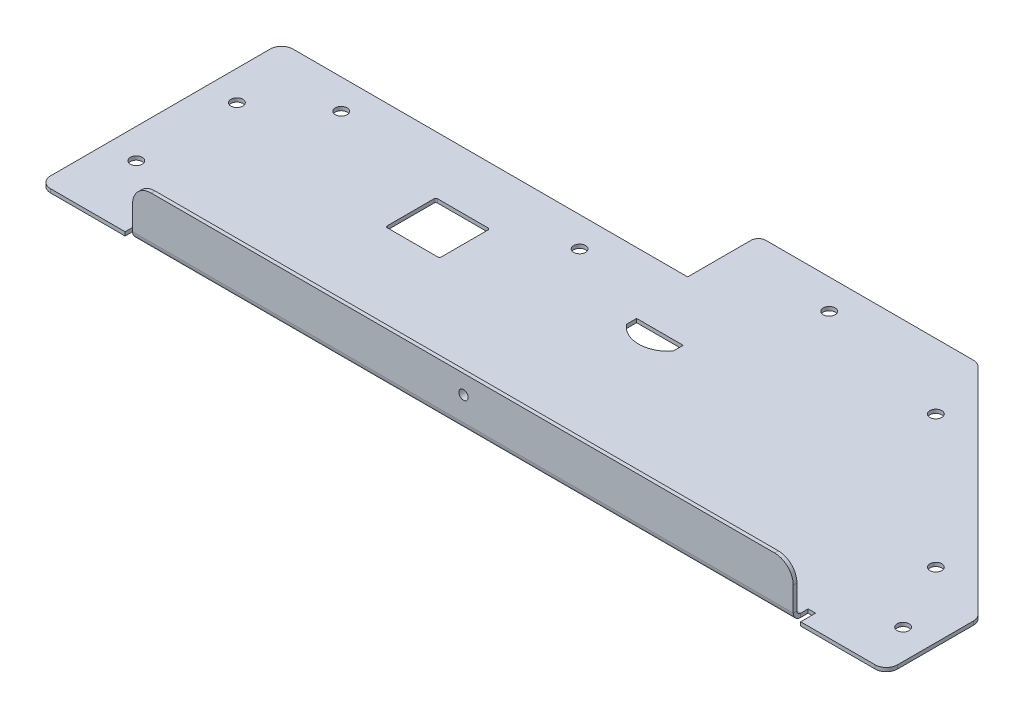
SolidWorks part; units mm, degrees
note: The reader was unsure of these and kept them because the rebuilt part matched: flange length of "边线-法兰1".
material "普通碳钢"
ref_plane "前视基准面" through (0, 0, 0) normal (0, 0, 1) x (1, 0, 0)
ref_plane "上视基准面" through (0, 0, 0) normal (0, 1, 0) x (1, 0, 0)
ref_plane "右视基准面" through (0, 0, 0) normal (1, 0, 0) x (0, 0, -1)
sketch "草图1" plane through (0, 0, 0) normal (0, 1, 0) x (1, 0, 0)
  line L0 (-322.3775, 0) -> (382.0821, 0) construction
  line L1 (0, 265.763) -> (0, -329.6125) construction
  line L2 (-113.67, 32.76) -> (-113.67, -26.24)
  line L3 (-110.67, -29.24) -> (110.67, -29.24)
  line L4 (113.67, -26.24) -> (113.67, -5.8826)
  line L5 (112.7913, -3.7613) -> (55.1487, 53.8813)
  line L6 (53.0274, 54.76) -> (-2.67, 54.76)
  line L7 (-4.67, 52.76) -> (-4.67, 35.76)
  line L8 (-4.67, 35.76) -> (-110.67, 35.76)
  line L9 (10.63, 19.26) -> (-1.87, 19.26)
  line L10 (-1.87, 19.26) -> (-1.87, 16.56)
  line L12 (10.63, 16.56) -> (10.63, 19.26)
  line L13 (-42.37, 19.86) -> (-42.37, 7.36)
  line L14 (-42.87, 6.86) -> (-56.37, 6.86)
  line L15 (-56.87, 7.36) -> (-56.87, 19.86)
  line L16 (-56.37, 20.36) -> (-42.87, 20.36)
  arc A0 (10.63, 16.56) -> (-1.87, 16.56) centre (4.38, 21.5537) cw
  arc A1 (-110.67, -29.24) -> (-113.67, -26.24) centre (-110.67, -26.24) cw
  arc A2 (-113.67, 32.76) -> (-110.67, 35.76) centre (-110.67, 32.76) cw
  arc A4 (55.1487, 53.8813) -> (53.0274, 54.76) centre (53.0274, 51.76) ccw
  arc A5 (113.67, -5.8826) -> (112.7913, -3.7613) centre (110.67, -5.8826) ccw
  arc A6 (110.67, -29.24) -> (113.67, -26.24) centre (110.67, -26.24) ccw
  circle A7 centre (-105.67, -11.24) radius 1.6
  circle A8 centre (-105.67, 15.76) radius 1.6
  circle A9 centre (-89.67, 27.76) radius 1.6
  circle A10 centre (-25.67, 27.76) radius 1.6
  circle A11 centre (22.33, 46.76) radius 1.6
  circle A12 centre (60.5163, 37.2) radius 1.6
  circle A13 centre (96.1163, 1.6) radius 1.6
  circle A14 centre (105.67, -16.74) radius 1.6
  arc A15 (-56.37, 20.36) -> (-56.87, 19.86) centre (-56.37, 19.86) ccw
  arc A16 (-56.87, 7.36) -> (-56.37, 6.86) centre (-56.37, 7.36) ccw
  arc A17 (-42.87, 6.86) -> (-42.37, 7.36) centre (-42.87, 7.36) ccw
  arc A18 (-42.37, 19.86) -> (-42.87, 20.36) centre (-42.87, 19.86) ccw
  arc A19 (-2.67, 54.76) -> (-4.67, 52.76) centre (-2.67, 52.76) ccw
  point P22 (4.38, 19.26)
  point P30 (54.27, 54.76)
  dimension "D11" = 8
  dimension "D13" = 3
  dimension "D18" = 3.2
  dimension "D32" = 0.5
  dimension "D33" = 2
  dimension "D34" = 3
  dimension "D1" = 65
  dimension "D2" = 109
  dimension "D3" = 19
  dimension "D4" = 58.94
  dimension "D5" = 227.34
  dimension "D6" = 45
  dimension "D7" = 40.5
  dimension "D8" = 12.5
  dimension "D9" = 14.5
  dimension "D10" = 13.5
  dimension "D12" = 2.7
  dimension "D14" = 18
  dimension "D15" = 27
  dimension "D16" = 24
  dimension "D17" = 64
  dimension "D19" = 8
  dimension "D20" = 8
  dimension "D21" = 27
  dimension "D22" = 8
  dimension "D23" = 8
  dimension "D24" = 8
  dimension "D25" = 17.56
  dimension "D26" = 35.6
  dimension "D27" = 12.5
  dimension "D28" = 8
  dimension "D29" = 15.4
  dimension "D30" = 16.5
  dimension "D31" = 56.8
base flange "基体-法兰1" sketch "草图1" thickness 1 reverse thickness direction no parameters "D1"=1
edge flange "边线-法兰1" sketch "草图4" flange angle 90 flange length 13.5 flange position material inside bend radius 1 thickness 1 relief rectangular parameters "D6"=10
sketch "草图4" plane through (0, 0, 29.24) normal (0, 0, 1) x (1, 0, 0)
  line L2 (-88.67, 0) -> (-88.67, 7.5)
  line L3 (-83.67, 12.5) -> (83.67, 12.5)
  line L4 (88.67, 7.5) -> (88.67, 0)
  line L5 (-110.67, 0) -> (110.67, 0) construction
  line L6 (-88.67, 0) -> (88.67, 0)
  line L7 (113.67, -1) -> (113.67, 0) construction
  line L8 (-113.67, -1) -> (-113.67, 0) construction
  line L9 (-110.67, -1) -> (110.67, -1) construction
  arc A0 (83.67, 12.5) -> (88.67, 7.5) centre (83.67, 7.5) cw
  arc A1 (-83.67, 12.5) -> (-88.67, 7.5) centre (-83.67, 7.5) ccw
  dimension "D3" = 5
  dimension "D1" = 25
  dimension "D2" = 25
  dimension "D4" = 13.5
bend "边线折弯1" bend radius 1 bend angle 90 parameters "D5"=1
sketch "草图5" plane through (0, 0, 28.24) normal (0, 0, -1) x (-1, 0, 0)
  line L0 (-88.67, -1) -> (88.67, -1) construction
  line L1 (113.67, -1) -> (113.67, 0) construction
  circle A0 centre (-0.17, 7.5) radius 3
  dimension "D1" = 6
  dimension "D2" = 8.5
  dimension "D3" = 113.84
extrude "凸台-拉伸1" add sketch "草图5" along normal blind 2
hole_wizard "M3 螺纹孔1" positions "草图6" profile "草图7" tap size "M3" standard "GB" end condition through all
sketch "草图6" plane through (0, 0, 26.24) normal (0, 0, -1) x (-1, 0, 0)
  point P0 (-0.17, 7.5)
sketch "草图7" plane through (0.17, 7.5, 26.24) normal (1, 0, 0) x (0, 1, 0)
  line L0 (0, 0) -> (0, 3)
  line L1 (0, 3) -> (1.25, 3)
  line L2 (1.25, 3) -> (1.25, 0)
  line L5 (1.25, 0) -> (0, 0)
  line L11 (0, -6.35) -> (0, 107.95) construction
  dimension "通孔螺纹孔钻头直径" = 2.5
  dimension "通孔螺纹孔钻头深度" = 3
cosmetic thread "孔螺蚊线1"
sketch "折弯-线1" [suppressed] plane through (0, 0, 0) normal (0, 1, 0) x (1, 0, 0)
sketch "边界框1" [suppressed] plane through (0, 0, 0) normal (0, 1, 0) x (1, 0, 0)
sheet metal parameters "钣金6" thickness 1 parameters "D1"=1
flat pattern "平板型式6" [suppressed]
sketch "折弯-线2" plane through (0, 0, 0) normal (0, 1, 0) x (1, 0, 0)
sketch3d "边界框2" [suppressed]
  line L0 (113.67, -31.612, 0) -> (-113.67, -31.612, 0) construction
  line L1 (113.67, 52.388, 0) -> (-113.67, 52.388, 0) construction
  line L2 (113.67, -31.612, 0) -> (113.67, 52.388, 0) construction
  line L3 (-113.67, -31.612, 0) -> (-113.67, 52.388, 0) construction
sheet metal parameters "钣金7" thickness 1 parameters "D1"=1
flat pattern "平板型式6" [suppressed]
sketch "折弯-线2" plane through (0, 0, 0) normal (0, 1, 0) x (1, 0, 0)
sketch3d "边界框2" [suppressed]
  line L0 (113.67, -31.612, 0) -> (-113.67, -31.612, 0) construction
  line L1 (113.67, 52.388, 0) -> (-113.67, 52.388, 0) construction
  line L2 (113.67, -31.612, 0) -> (113.67, 52.388, 0) construction
  line L3 (-113.67, -31.612, 0) -> (-113.67, 52.388, 0) construction
bend of the flat pattern "展开-<边线折弯1>1"
sheet metal parameters "钣金8" thickness 1 parameters "D1"=1
flat pattern "平板型式6" [suppressed]
sketch "折弯-线2" plane through (0, 0, 0) normal (0, 1, 0) x (1, 0, 0)
sketch3d "边界框2" [suppressed]
  line L0 (113.67, -31.612, 0) -> (-113.67, -31.612, 0) construction
  line L1 (113.67, 52.388, 0) -> (-113.67, 52.388, 0) construction
  line L2 (113.67, -31.612, 0) -> (113.67, 52.388, 0) construction
  line L3 (-113.67, -31.612, 0) -> (-113.67, 52.388, 0) construction
bend of the flat pattern "展开-<边线折弯1>1"
sheet metal parameters "钣金9" thickness 1 parameters "D1"=1
flat pattern "平板型式6"
sketch "折弯-线2" plane through (0, 0, 0) normal (0, 1, 0) x (-1, 0, 0)
  line L0 (88.67, 28.4181) -> (-88.67, 28.4181) construction
  line L1 (88.67, 28.4181) -> (-88.67, 28.4181) construction
sketch3d "边界框2" [suppressed]
  line L0 (3, 14.8562, 0) -> (-224.34, 14.8562, 0) construction
  line L1 (3, -81, 0) -> (-224.34, -81, 0) construction
  line L2 (3, 14.8562, 0) -> (3, -81, 0) construction
  line L3 (-224.34, 14.8562, 0) -> (-224.34, -81, 0) construction
bend of the flat pattern "展开-<边线折弯1>1"
